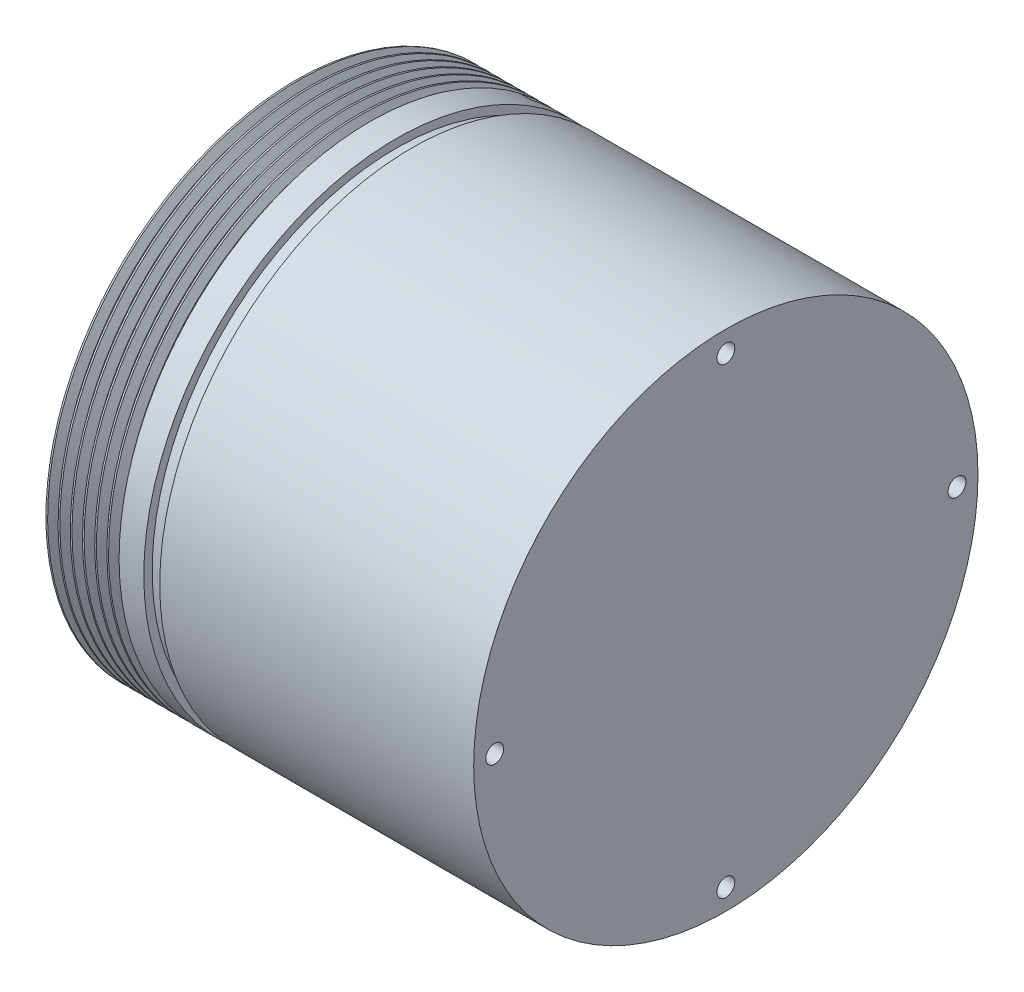
SolidWorks part; units mm, degrees
material "PE High Density"
ref_plane "Front Plane" through (0, 0, 0) normal (0, 0, 1) x (1, 0, 0)
ref_plane "Top Plane" through (0, 0, 0) normal (0, 1, 0) x (1, 0, 0)
ref_plane "Right Plane" through (0, 0, 0) normal (1, 0, 0) x (0, 0, -1)
sketch "Sketch1" plane through (0, 0, 0) normal (0, 0, 1) x (1, 0, 0)
  line L0 (0, 38.1) -> (0, 0)
  line L1 (0, 38.1) -> (-65.0875, 38.1)
  line L2 (-65.0875, 38.1) -> (-65.0875, 31.75)
  line L3 (-65.0875, 31.75) -> (-1.5875, 31.75)
  line L4 (-1.5875, 31.75) -> (-1.5875, 0)
  line L5 (-1.5875, 0) -> (0, 0)
  line L6 (0, 0) -> (-52.3875, 0) construction
  dimension "D2" = 63.5
  dimension "Wall Thickness" = 6.35
  dimension "Depth" = 63.5
  dimension "Front_Thickness" = 1.5875
revolve "Revolve1" add sketch "Sketch1" angle 360 about L6
sketch "Sketch5" plane through (-65.0875, 0, 0) normal (-1, 0, 0) x (0, 0, 1)
  circle A0 centre (0, 0) radius 33.3375
  circle A1 centre (0, 0) radius 35.8775
  dimension "oring inner" = 66.675
  dimension "oring width" = 2.54
extrude "Cut-Extrude1" cut sketch "Sketch5" against normal blind 1.27
sketch "Sketch2" plane through (0, 0, 0) normal (0, 0, 1) x (1, 0, 0)
  line L0 (-65.0875, 38.1) -> (-65.0875, -38.1) construction
  line L12 (-66.675, 38.1) -> (-65.0875, 38.1)
  line L13 (-65.0875, 38.1) -> (-65.7542, 36.9452)
  line L14 (-65.7542, 36.9452) -> (-66.0083, 36.9452)
  line L15 (-66.0083, 36.9452) -> (-66.675, 38.1)
  line L16 (-65.8813, 36.9452) -> (-65.8813, 38.1) construction
  dimension "D1" = 0.254
  dimension "D3" = 1.5875
  dimension "D5" = 60
sketch "Sketch4" plane through (-65.0875, 0, 0) normal (-1, 0, 0) x (0, 0, 1)
  circle A0 centre (0, 0) radius 38.1
  circle A1 centre (0, 0) radius 38.1 construction
curve "Helix/Spiral1" pitch 1.8415 height 12.7 radius 38.1 centre (-65.0875, 0, 0) axis (1, 0, 0) start towards (0, 1, 0)
sweep "Cut-Sweep2" cut profiles "Sketch2" path "Helix/Spiral1"
hole_wizard "#6-32 Tapped Hole1" positions "Sketch11" profile "Sketch10" tap size "#6-32" standard "ANSI Inch"
sketch "Sketch11" plane through (0, 0, 0) normal (1, 0, 0) x (0, 0, -1)
  line L0 (0, 31.75) -> (0, 38.1) construction
  line L3 (-31.75, 0) -> (-38.1, 0) construction
  line L6 (0, -31.75) -> (0, -38.1) construction
  line L9 (31.75, 0) -> (38.1, 0) construction
  circle A0 centre (0, 0) radius 31.75 construction
  circle A1 centre (0, 0) radius 31.75
  circle A2 centre (0, 0) radius 38.1 construction
  circle A3 centre (0, 0) radius 38.1
  point P31 (0, 34.925)
  point P33 (34.925, 0)
  point P35 (0, -34.925)
  point P37 (-34.925, 0)
sketch "Sketch10" plane through (0, 34.925, 0) normal (0, 1, 0) x (0, 0, -1)
  line L0 (0, 0) -> (0, 11.8871)
  line L1 (0, 11.8871) -> (1.3525, 11.0744)
  line L2 (1.3525, 11.0744) -> (1.3525, 0)
  line L5 (1.3525, 0) -> (0, 0)
  line L10 (0, 11.8871) -> (-1.3525, 11.0744) construction
  line L11 (0, -6.35) -> (0, 107.95) construction
  dimension "Tap Drill Dia." = 2.7051
  dimension "Tap Drill Depth" = 11.0744
  dimension "Drill Angle" = 118
sketch "Sketch14" plane through (0, 0, 0) normal (0, 0, 1) x (1, 0, 0)
  line L1 (-49.8475, 38.1) -> (-47.4345, 38.1)
  line L2 (0, 38.1) -> (-65.0875, 38.1) construction
  line L4 (-49.8475, 38.1) -> (-49.8475, 36.83)
  line L5 (-49.8475, 36.83) -> (-47.4345, 36.83)
  line L6 (-47.4345, 36.83) -> (-47.4345, 38.1)
  line L7 (-65.0875, 38.1) -> (-65.0875, -23.8848) construction
  line L8 (0, 0) -> (-45.4343, 0) construction
  dimension "D1" = 2.413
  dimension "D2" = 1.27
  dimension "D3" = 15.24
revolve "Cut-Revolve1" cut sketch "Sketch14" angle 360 about L8
